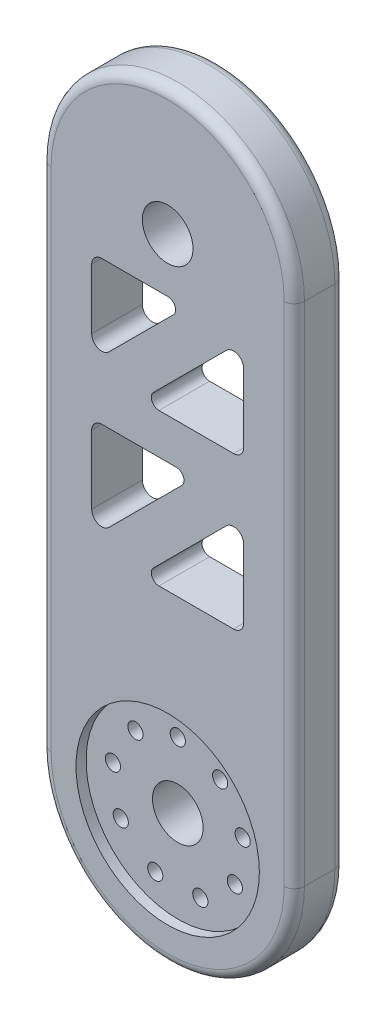
SolidWorks part; units mm, degrees
ref_plane "Front Plane" through (0, 0, 0) normal (0, 0, 1) x (1, 0, 0)
ref_plane "Top Plane" through (0, 0, 0) normal (0, 1, 0) x (1, 0, 0)
ref_plane "Right Plane" through (0, 0, 0) normal (1, 0, 0) x (0, 0, -1)
sketch "Sketch1" plane through (0, 0, 0) normal (0, 0, 1) x (1, 0, 0)
  line L0 (15, 0) -> (15, 100)
  line L2 (0, 0) -> (0, 100)
  line L4 (50, 0) -> (50, 100)
  line L5 (35, 0) -> (35, 100)
  arc A0 (50, 100) -> (0, 100) centre (25, 100) ccw
  arc A1 (0, 0) -> (50, 0) centre (25, 0) ccw
  circle A2 centre (25, 0) radius 5
  circle A3 centre (25, 100) radius 5
  arc A4 (35, 100) -> (15, 100) centre (25, 100) ccw
  arc A5 (15, 0) -> (35, 0) centre (25, 0) ccw
  dimension "D3" = 10
  dimension "D4" = 10
  dimension "D1" = 100
  dimension "D2" = 50
  dimension "D5" = 15
extrude "Boss-Extrude1" add sketch "Sketch1" along normal blind 10 contours L2 A1 L4 A0 A5 L0 A4 L5 | L0 A5 L5 A4 A2 A3 region at (25, 50, 0) region at (1.5811, 50, 0)
sketch "Sketch2" plane through (0, 0, 10) normal (0, 0, 1) x (1, 0, 0)
  line L0 (10, 100) -> (10, 0)
  line L1 (40, 0) -> (40, 100)
  line L2 (0, 100) -> (0, 0)
  line L3 (50, 0) -> (50, 100)
  line L4 (0, 100) -> (0, 0)
  line L5 (50, 0) -> (50, 100)
  line L6 (25, 99) -> (25, 100) construction
  line L7 (25.065, 89.3431) -> (10, 89.3431)
  line L16 (23.2782, 9) -> (40, 9)
  line L17 (40, 29.3431) -> (22.2175, 11.5607)
  line L18 (23.2782, 39) -> (40, 39)
  line L19 (27.8284, 47.1716) -> (22.2175, 41.5607)
  line L20 (27.8284, 47.1716) -> (40, 59.3431)
  line L21 (40, 69) -> (23.2782, 69)
  line L22 (22.2175, 71.5607) -> (40, 89.3431)
  line L25 (27.7825, 28.4393) -> (10, 10.6569)
  line L26 (10, 31) -> (26.7218, 31)
  line L27 (22.1716, 52.8284) -> (10, 40.6569)
  line L28 (22.1716, 52.8284) -> (27.7825, 58.4393)
  line L29 (26.7218, 61) -> (10, 61)
  line L30 (10, 70.6569) -> (26.1256, 86.7825)
  line L47 (25, 89.3431) -> (25, 91) construction
  arc A0 (10, 0) -> (40, 0) centre (25, 0) ccw
  arc A1 (40, 100) -> (10, 100) centre (25, 100) ccw
  arc A2 (0, 0) -> (50, 0) centre (25, 0) ccw
  arc A3 (50, 100) -> (0, 100) centre (25, 100) ccw
  arc A4 (0, 0) -> (50, 0) centre (25, 0) ccw
  arc A5 (50, 100) -> (0, 100) centre (25, 100) ccw
  arc A6 (26.1256, 86.7825) -> (25.065, 89.3431) centre (25.065, 87.8431) ccw
  arc A7 (22.2175, 71.5607) -> (23.2782, 69) centre (23.2782, 70.5) ccw
  arc A8 (26.7218, 61) -> (27.7825, 58.4393) centre (26.7218, 59.5) cw
  arc A9 (22.2175, 41.5607) -> (23.2782, 39) centre (23.2782, 40.5) ccw
  arc A10 (26.7218, 31) -> (27.7825, 28.4393) centre (26.7218, 29.5) cw
  arc A11 (22.2175, 11.5607) -> (23.2782, 9) centre (23.2782, 10.5) ccw
  dimension "D3" = 1.5
  dimension "D1" = 0
  dimension "D2" = 10
extrude "Cut-Extrude2" cut sketch "Sketch2" against normal blind 10 contours L30 A6 L7 L0 | L22 A7 L21 L1 | A8 L29 L0 L27 L28 | L19 A9 L18 L1 L20 region at (16.0531, 83.0243, 10) region at (33.3818, 75.8644, 10) region at (16.6182, 54.1356, 10) region at (33.3818, 45.8644, 10)
fillet "Fillet1" radius 2 8 edges at (40, 89.3431, 5) (40, 69, 5) (10, 89.3431, 5) (10, 70.6569, 5) (10, 40.6569, 5) (10, 61, 5) (40, 59.3431, 5) (40, 39, 5)
fillet "Fillet2" radius 2 8 edges at (25, -25, 10) (50, 50, 10) (25, 125, 10) (25, -25, 0) (50, 50, 0) (25, 125, 0) (0, 50, 10) (0, 50, 0)
sketch "Sketch3" plane through (0, 0, 10) normal (0, 0, 1) x (1, 0, 0)
  circle A0 centre (25, 0) radius 18.1
  dimension "D1" = 36.2
extrude "Cut-Extrude3" cut sketch "Sketch3" against normal blind 2
sketch "Sketch4" plane through (0, 0, 0) normal (0, 0, -1) x (-1, 0, 0)
  line L0 (-25, 0) -> (-25, 13) construction
  circle A0 centre (-25, 13) radius 1.5
  circle A1 centre (-25, 13) radius 3
  dimension "D2" = 6
  dimension "D3" = 3
  dimension "D1" = 13
extrude "Cut-Extrude4" cut sketch "Sketch4" against normal through all contours A0
extrude "Cut-Extrude5" cut sketch "Sketch4<3>" against normal blind 2
sketch "Sketch4<3>" plane through (0, 0, 0) normal (0, 0, -1) x (-1, 0, 0) same geometry as "Sketch4"
ref_axis "Axis1" through (25, 0, 8) along (0, 0, -1)
pattern_circular "CirPattern1" count 9 every 40 about axis through (25, 0, 8) along (0, 0, -1) of "Cut-Extrude5", "Cut-Extrude4"
